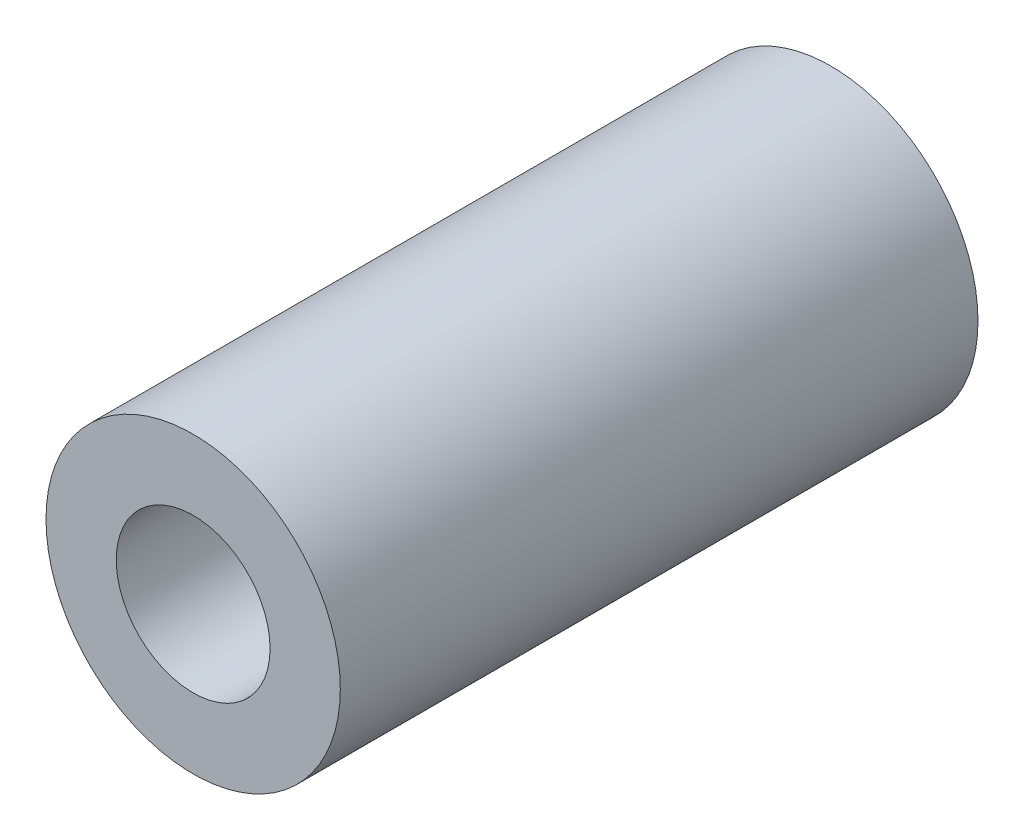
SolidWorks part; units mm, degrees
material "6061-T6 (SS)"
ref_plane "Front Plane" through (0, 0, 0) normal (0, 0, 1) x (1, 0, 0)
ref_plane "Top Plane" through (0, 0, 0) normal (0, 1, 0) x (1, 0, 0)
ref_plane "Right Plane" through (0, 0, 0) normal (1, 0, 0) x (0, 0, -1)
sketch "Sketch1" plane through (0, 0, 0) normal (0, 0, 1) x (1, 0, 0)
  circle A0 centre (0, 0) radius 2.4892
  circle A1 centre (0, 0) radius 4.7625
  dimension "D1" = 9.525
  dimension "D2" = 4.9784
extrude "Boss-Extrude1" add sketch "Sketch1" along normal mid plane 20.6375
